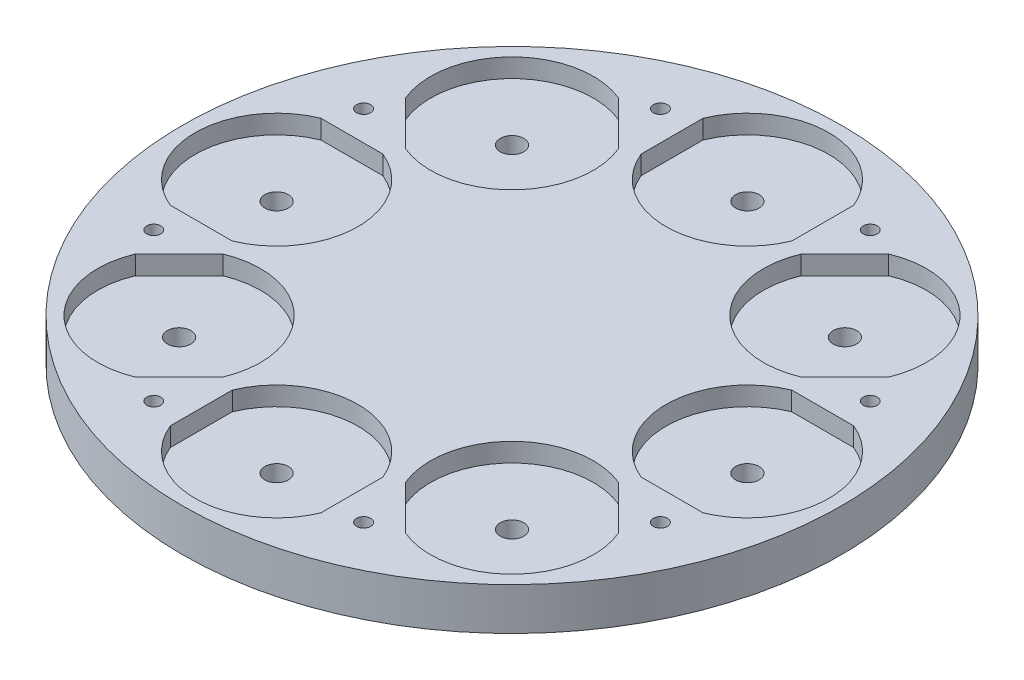
SolidWorks part; units mm, degrees
ref_plane "Front Plane" through (0, 0, 0) normal (0, 0, 1) x (1, 0, 0)
ref_plane "Top Plane" through (0, 0, 0) normal (0, 1, 0) x (1, 0, 0)
ref_plane "Right Plane" through (0, 0, 0) normal (1, 0, 0) x (0, 0, -1)
sketch "Sketch1" plane through (0, 0, 0) normal (0, 1, 0) x (1, 0, 0)
  line L0 (70, 0) -> (50, 0) construction
  circle A0 centre (0, 0) radius 70
  circle A1 centre (50, 0) radius 12
  circle A2 centre (35.3553, -35.3553) radius 12
  circle A3 centre (0, -50) radius 12
  circle A4 centre (-35.3553, -35.3553) radius 12
  circle A5 centre (-50, 0) radius 12
  circle A6 centre (-35.3553, 35.3553) radius 12
  circle A7 centre (0, 50) radius 12
  circle A8 centre (35.3553, 35.3553) radius 12
  point P23 (0, 0)
  dimension "D1" = 140
  dimension "D3" = 24
  dimension "D2" = 20
  dimension "D4" = 8
extrude "Boss-Extrude1" add sketch "Sketch1" along normal blind 25
sketch "Sketch2" plane through (0, 25, 0) normal (0, 1, 0) x (1, 0, 0)
  line L0 (50, 0) -> (50, 16) construction
  line L1 (50, 16) -> (43.4205, 16)
  line L2 (50, 16) -> (56.5795, 16)
  line L3 (32.7, 0) -> (67.3, 0) construction
  line L4 (50, -16) -> (56.5795, -16)
  line L5 (50, -16) -> (43.4205, -16)
  line L6 (46.669, -24.0416) -> (42.0166, -19.3892)
  line L7 (24.0416, -46.669) -> (19.3892, -42.0166)
  line L8 (24.0416, -46.669) -> (28.694, -51.3215)
  line L9 (46.669, -24.0416) -> (51.3215, -28.694)
  line L10 (16, -50) -> (16, -43.4205)
  line L11 (-16, -50) -> (-16, -43.4205)
  line L12 (-16, -50) -> (-16, -56.5795)
  line L13 (16, -50) -> (16, -56.5795)
  line L14 (-24.0416, -46.669) -> (-19.3892, -42.0166)
  line L15 (-46.669, -24.0416) -> (-42.0166, -19.3892)
  line L16 (-46.669, -24.0416) -> (-51.3215, -28.694)
  line L17 (-24.0416, -46.669) -> (-28.694, -51.3215)
  line L18 (-50, -16) -> (-43.4205, -16)
  line L19 (-50, 16) -> (-43.4205, 16)
  line L20 (-50, 16) -> (-56.5795, 16)
  line L21 (-50, -16) -> (-56.5795, -16)
  line L22 (-46.669, 24.0416) -> (-42.0166, 19.3892)
  line L23 (-24.0416, 46.669) -> (-19.3892, 42.0166)
  line L24 (-24.0416, 46.669) -> (-28.694, 51.3215)
  line L25 (-46.669, 24.0416) -> (-51.3215, 28.694)
  line L26 (-16, 50) -> (-16, 43.4205)
  line L27 (16, 50) -> (16, 43.4205)
  line L28 (16, 50) -> (16, 56.5795)
  line L29 (-16, 50) -> (-16, 56.5795)
  line L30 (24.0416, 46.669) -> (19.3892, 42.0166)
  line L31 (46.669, 24.0416) -> (42.0166, 19.3892)
  line L32 (46.669, 24.0416) -> (51.3215, 28.694)
  line L33 (24.0416, 46.669) -> (28.694, 51.3215)
  arc A0 (43.4205, 16) -> (43.4205, -16) centre (50, 0) ccw
  arc A1 (56.5795, -16) -> (56.5795, 16) centre (50, 0) ccw
  arc A2 (42.0166, -19.3892) -> (19.3892, -42.0166) centre (35.3553, -35.3553) ccw
  arc A3 (28.694, -51.3215) -> (51.3215, -28.694) centre (35.3553, -35.3553) ccw
  arc A4 (16, -43.4205) -> (-16, -43.4205) centre (0, -50) ccw
  arc A5 (-16, -56.5795) -> (16, -56.5795) centre (0, -50) ccw
  arc A6 (-19.3892, -42.0166) -> (-42.0166, -19.3892) centre (-35.3553, -35.3553) ccw
  arc A7 (-51.3215, -28.694) -> (-28.694, -51.3215) centre (-35.3553, -35.3553) ccw
  arc A8 (-43.4205, -16) -> (-43.4205, 16) centre (-50, 0) ccw
  arc A9 (-56.5795, 16) -> (-56.5795, -16) centre (-50, 0) ccw
  arc A10 (-42.0166, 19.3892) -> (-19.3892, 42.0166) centre (-35.3553, 35.3553) ccw
  arc A11 (-28.694, 51.3215) -> (-51.3215, 28.694) centre (-35.3553, 35.3553) ccw
  arc A12 (-16, 43.4205) -> (16, 43.4205) centre (0, 50) ccw
  arc A13 (16, 56.5795) -> (-16, 56.5795) centre (0, 50) ccw
  arc A14 (19.3892, 42.0166) -> (42.0166, 19.3892) centre (35.3553, 35.3553) ccw
  arc A15 (51.3215, 28.694) -> (28.694, 51.3215) centre (35.3553, 35.3553) ccw
  point P61 (0, 0)
  dimension "D1" = 34.6
  dimension "D2" = 16
  dimension "D3" = 8
extrude "Cut-Extrude1" cut sketch "Sketch2" against normal blind 10
ref_plane "Plane1" through (0, 10, 0) normal (0, 1, 0) x (1, 0, 0)
split "Split1" trim tools "Plane1" bodies to split 102 resulting bodies 103 104
delete or keep bodies "Body-Delete/Keep 1" type delete bodies bodies 104
sketch "Sketch3" plane through (0, 10, 0) normal (0, -1, 0) x (1, 0, 0)
  circle A0 centre (0, 0) radius 20
  dimension "D1" = 40
extrude "Cut-Extrude2" cut sketch "Sketch3" against normal blind 7.5
sketch "Sketch4" plane through (0, 25, 0) normal (0, 1, 0) x (1, 0, 0)
  circle A0 centre (0, 0) radius 70
extrude "Cut-Extrude3" cut sketch "Sketch4" against normal blind 6
sketch "Sketch5" plane through (0, 19, 0) normal (0, 1, 0) x (1, 0, 0)
  line L0 (-70, 0) -> (70, 0) construction
  line L1 (0, 4) -> (0, -4) construction
  circle A1 centre (0, 0) radius 70 construction
  circle A2 centre (0, -4) radius 1.5
  circle A3 centre (0, 4) radius 1.5
  circle A4 centre (-4, 0) radius 1.5
  circle A5 centre (4, 0) radius 1.5
  point P11 (0, 0)
  dimension "D1" = 3
  dimension "D3" = 4
  dimension "D2" = 8
extrude "Cut-Extrude4" cut sketch "Sketch5" against normal through all
sketch "Sketch6" plane through (0, 19, 0) normal (0, 1, 0) x (1, 0, 0)
  line L0 (-16, 43.4205) -> (-19.3892, 42.0166) construction
  line L1 (-17.6946, 42.7186) -> (-26.7878, 64.6716) construction
  circle A0 centre (0, 0) radius 70 construction
  circle A1 centre (-22.2868, 53.8051) radius 1.5
  circle A2 centre (22.2868, 53.8051) radius 1.5
  circle A3 centre (53.8051, 22.2868) radius 1.5
  circle A4 centre (53.8051, -22.2868) radius 1.5
  circle A5 centre (22.2868, -53.8051) radius 1.5
  circle A6 centre (-22.2868, -53.8051) radius 1.5
  circle A7 centre (-53.8051, -22.2868) radius 1.5
  circle A8 centre (-53.8051, 22.2868) radius 1.5
  point P19 (0, 0)
  dimension "D1" = 12
  dimension "D3" = 3
  dimension "D2" = 21.953
  dimension "D4" = 8
sketch "Sketch7" plane through (0, 17.5, 0) normal (0, -1, 0) x (1, 0, 0)
  circle A0 centre (0, 0) radius 20
extrude "Boss-Extrude2" add sketch "Sketch7" along normal up to surface and the other way up to surface up to face at (0, 10, -20) other way up to face at (0, 19, 5.5)
sketch "Sketch9" plane through (0, 10, 0) normal (0, -1, 0) x (1, 0, 0)
  circle A0 centre (0, 50) radius 12
  circle A1 centre (0, 50) radius 2.4904
  circle A2 centre (35.3553, 35.3553) radius 2.4904
  circle A3 centre (35.3553, 35.3553) radius 12
  circle A4 centre (50, 0) radius 2.4904
  circle A5 centre (50, 0) radius 12
  circle A6 centre (35.3553, -35.3553) radius 2.4904
  circle A7 centre (35.3553, -35.3553) radius 12
  circle A8 centre (0, -50) radius 2.4904
  circle A9 centre (0, -50) radius 12
  circle A10 centre (-35.3553, -35.3553) radius 2.4904
  circle A11 centre (-35.3553, -35.3553) radius 12
  circle A12 centre (-50, 0) radius 2.4904
  circle A13 centre (-50, 0) radius 12
  circle A14 centre (-35.3553, 35.3553) radius 2.4904
  circle A15 centre (-35.3553, 35.3553) radius 12
  point P28 (0, 0)
  dimension "D1" = 8
extrude "Boss-Extrude3" add sketch "Sketch9" against normal up to surface (5 mm away) up to face at (50, 15, 12)
extrude "Cut-Extrude5" cut sketch "Sketch6" against normal through all
